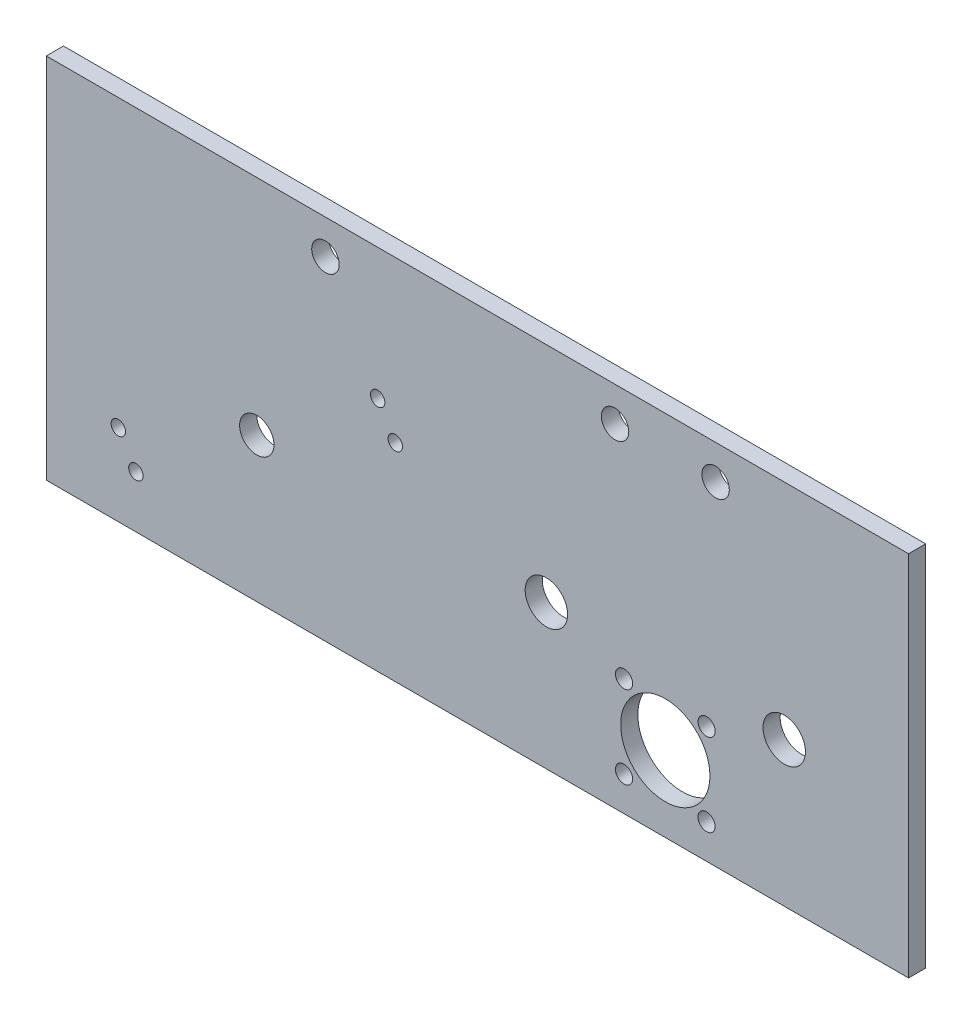
SolidWorks part; units mm, degrees
ref_plane "Спереди" through (0, 0, 0) normal (0, 0, 1) x (1, 0, 0)
ref_plane "Сверху" through (0, 0, 0) normal (0, 1, 0) x (1, 0, 0)
ref_plane "Справа" through (0, 0, 0) normal (1, 0, 0) x (0, 0, -1)
sketch "Эскиз1" plane through (0, 0, 0) normal (0, 0, 1) x (1, 0, 0)
  line L0 (-12.0208, 12.0208) -> (0, 0) construction
  line L1 (-180.3069, 85) -> (70.8528, 85)
  line L2 (-180.3069, 85) -> (-180.3069, -22.0208)
  line L3 (-180.3069, -22.0208) -> (70.8528, -22.0208)
  line L4 (70.8528, 85) -> (70.8528, -22.0208)
  line L5 (0, 0) -> (0, 85) construction
  line L6 (-34.641, 20) -> (0, 0) construction
  circle A0 centre (0, 0) radius 13
  circle A1 centre (-12.0208, 12.0208) radius 2.5
  circle A2 centre (12.0208, 12.0208) radius 2.5
  circle A3 centre (12.0208, -12.0208) radius 2.5
  circle A4 centre (-12.0208, -12.0208) radius 2.5
  circle A5 centre (-34.641, 20) radius 6.1833
  circle A6 centre (34.641, 20) radius 6.1833
  circle A7 centre (-118.9916, 20) radius 5
  circle A8 centre (-14.641, 75) radius 4
  circle A9 centre (14.641, 75) radius 4
  circle A10 centre (-98.9916, 75) radius 4
  point P19 (0, 0)
  dimension "D2" = 5
  dimension "D4" = 26
  dimension "D9" = 8
  dimension "D1" = 45
  dimension "D3" = 17
  dimension "D6" = 55
  dimension "D7" = 20
  dimension "D8" = 20
  dimension "D10" = 10
  dimension "D11" = 10
  dimension "D12" = 40
  dimension "D13" = 20
  dimension "D5" = 4
extrude "Бобышка-Вытянуть1" add sketch "Эскиз1" along normal blind 5
hole_wizard "Отверстие обработанное метчиком M51" positions "Эскиз2" profile "Эскиз4" tap size "M5" standard "ISO" end condition through all
sketch "Эскиз2" plane through (0, 0, 0) normal (0, 0, -1) x (-1, 0, 0)
  point P0 (159.3306, 1.7307)
  point P3 (154.2029, -6.8545)
  point P6 (83.7803, 46.8545)
  point P9 (78.6526, 38.2693)
sketch "Эскиз4" plane through (-159.3306, 1.7307, 0) normal (1, 0, 0) x (0, 1, 0)
  line L0 (0, 0) -> (0, 5)
  line L1 (0, 5) -> (2.1, 5)
  line L2 (2.1, 5) -> (2.1, 0)
  line L5 (2.1, 0) -> (0, 0)
  line L11 (0, -6.35) -> (0, 107.95) construction
  dimension "Диаметр проходного сверла" = 4.2
  dimension "Глубина проходного сверла" = 5
cosmetic thread "Отверстие резьбы1" parameters "D2"=5
cosmetic thread "Отверстие резьбы2" parameters "D2"=5
cosmetic thread "Отверстие резьбы3" parameters "D2"=5
cosmetic thread "Отверстие резьбы4" parameters "D2"=5
equation "\"Диаметр резьбы редуктора\" = 4  'Диаметр резьбы на фланце"
equation "\"Глубина резьбы редуктора\" = 7  'Диаметр резьбы на фланце"
equation "\"Диаметр окружности расположения редуктора\" = 34  'Диаметр расположения резьбы на фланце"
equation "\"Диаметр бурта редуктора\" = 26  'Диаметр бурта на фланце (Посадка h7)"
equation "\"Угл сдвига редуктора\" = 45"
equation "\"D1@Эскиз1\"=\"Угл сдвига редуктора\""
equation "\"D2@Эскиз1\"=\"Диаметр резьбы редуктора\"+1"
equation "\"D3@Эскиз1\"=\"Диаметр окружности расположения редуктора\"/2"
equation "\"D4@Эскиз1\"=\"Диаметр бурта редуктора\""
equation "\"Толщина пластины\" = 5"
equation "\"Межосевое прижима Вертикаль\" = 15  '!!!"
equation "\"Межосевое прижима Горизонталь\" = 20  '!!!"
equation "\"D7@Эскиз1\"=\"Межосевое прижима Горизонталь\""
equation "\"D8@Эскиз1\"=\"Межосевое прижима Горизонталь\""
equation "\"D1@Бобышка-Вытянуть1\"=\"Толщина пластины\""
equation "\"D6@Эскиз1\"=\"Межосевое прижима Вертикаль\"+\"Внешний диаметр ролика\""
equation "\"Внешний диаметр ролика\" = 40  'Внешний диаметр ролика"
equation "\"Диаметр вала ролика\" = 8  '!!!"
equation "\"D9@Эскиз1\"=\"Диаметр вала ролика\""
